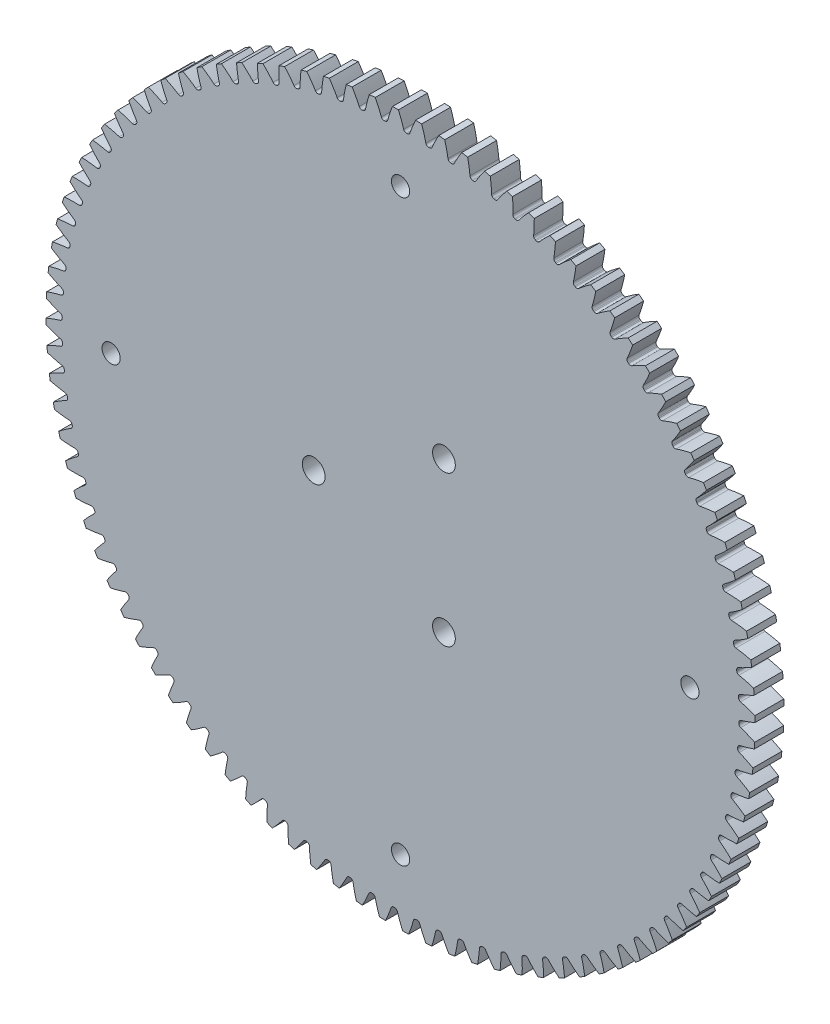
SolidWorks part; units mm, degrees
ref_plane "Front" through (0, 0, 0) normal (0, 0, 1) x (1, 0, 0)
ref_plane "Top" through (0, 0, 0) normal (0, 1, 0) x (1, 0, 0)
ref_plane "Right" through (0, 0, 0) normal (1, 0, 0) x (0, 0, -1)
sketch "Sketch3" plane through (0, 0, 0) normal (0, 0, 1) x (1, 0, 0)
  circle A0 centre (0, 0) radius 77.7875
  dimension "od" = 155.575
extrude "gearBody" add sketch "Sketch3" along normal blind 6.35
sketch "Sketch2" plane through (0, 0, 0) normal (0, 0, 1) x (1, 0, 0)
  line L0 (0, 0) -> (66.154, 27.4019) construction
  line L1 (89.9379, -14.1817) -> (0, 0) construction
  line L2 (0, 0) -> (36.3143, 0) construction
  line L3 (76.1998, -0.172) -> (76.1546, -2.6294) construction
  line L5 (76.1772, -1.4007) -> (0, 0) construction
  line L7 (0, 0) -> (71.6046, 0) construction
  arc A0 (71.5902, -1.4371) -> (71.5946, -1.1957) centre (0, 0) ccw construction
  arc A1 (77.7861, 0.4588) -> (77.7167, -3.3181) centre (0, 0) ccw construction
  arc A2 (76.1998, -0.172) -> (76.1546, -2.6294) centre (0, 0) ccw construction
  arc A3 (74.2296, -1.47) -> (74.2335, -1.2598) centre (0, 0) ccw
  arc A4 (89.9379, -14.1817) -> (74.6441, -2.0632) centre (65.1019, -29.8153) ccw
  arc A5 (89.9379, -14.1817) -> (90.3984, 10.8657) centre (0, 0) ccw
  arc A6 (90.3984, 10.8657) -> (74.6695, -0.6823) centre (66.154, 27.4019) cw
  arc A7 (74.2335, -1.2598) -> (74.6695, -0.6823) centre (74.8478, -1.2702) cw
  arc A8 (74.6441, -2.0632) -> (74.2296, -1.47) centre (74.8439, -1.4822) cw
  point P6 (90.3984, 10.8657)
  point P22 (89.9379, -14.1817)
  dimension "baseDia" = 143.2092
  dimension "od" = 155.575
  dimension "pd" = 152.4
  dimension "rd" = 148.4884
  dimension "rFillet" = 0.6144
  dimension "pointX" = 90.3984
  dimension "pointY" = 10.8657
  dimension "CTT" = 2.4574
  dimension "flankCenterAngle" = 22.5
extrude "toothCut" cut sketch "Sketch2" along normal through all
pattern_circular "CirPattern1" count 96 over 360 about axis through (0, 0, 6.35) along (0, 0, -1) of "toothCut"
sketch "hub1Dia" plane through (0, 0, 0) normal (0, 0, -1) x (-1, 0, 0)
  circle A0 centre (0, 0) radius 12.7
  dimension "hub1Dia" = 25.4
sketch "hub2Dia" plane through (0, 0, 6.35) normal (0, 0, 1) x (1, 0, 0)
  circle A0 centre (0, 0) radius 12.7
  dimension "hub2dia" = 25.4
sketch "boreDia" plane through (0, 0, 0) normal (0, 0, 1) x (1, 0, 0)
  circle A0 centre (0, 0) radius 7.9375
  dimension "boreDia" = 15.875
sketch "Sketch4" plane through (0, 0, 0) normal (0, 0, -1) x (-1, 0, 0)
  circle A0 centre (19.05, 0) radius 2.5
  circle A1 centre (-9.525, -16.4978) radius 2.5
  circle A2 centre (-9.525, 16.4978) radius 2.5
  point P10 (0, 0)
  dimension "D2" = 5
  dimension "D1" = 19.05
  dimension "D3" = 3
extrude "Cut-Extrude1" cut sketch "Sketch4" against normal through all
sketch "Sketch5" plane through (0, 0, 0) normal (0, 0, -1) x (-1, 0, 0)
  circle A0 centre (63.5, 0) radius 2
  circle A1 centre (0, -63.5) radius 2
  circle A2 centre (-63.5, 0) radius 2
  circle A3 centre (0, 63.5) radius 2
  point P12 (0, 0)
  dimension "D1" = 4
  dimension "D2" = 63.5
  dimension "D3" = 4
extrude "Cut-Extrude2" cut sketch "Sketch5" against normal through all
equation "\"D2@Sketch4\"=5mm"
equation "\"D1@Sketch5\"=4mm"
